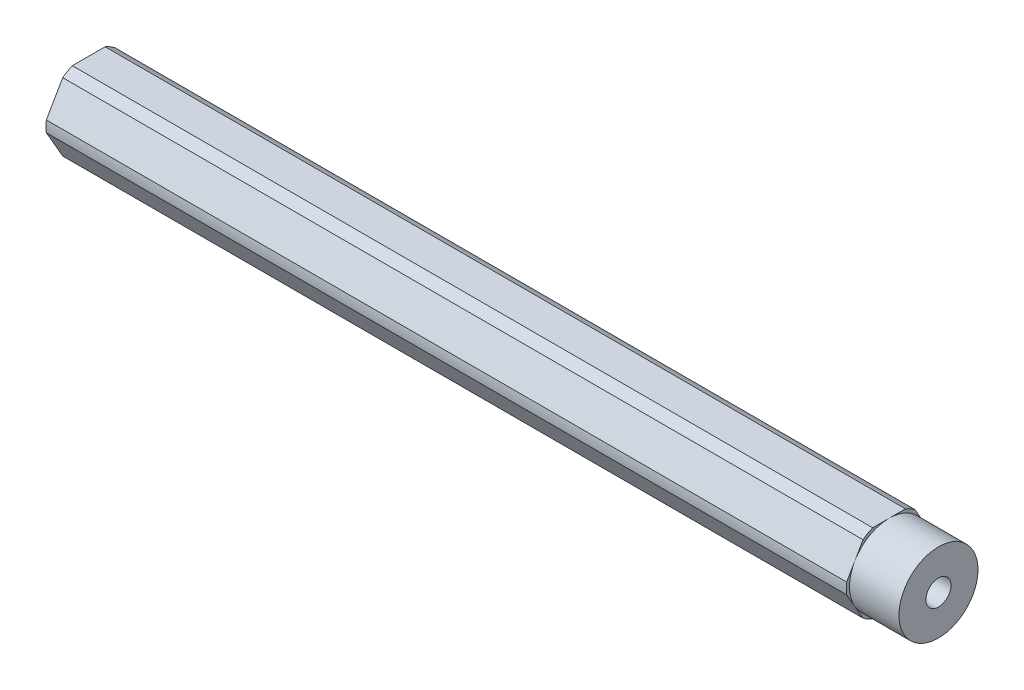
SolidWorks part; units mm, degrees
material "7075-T6 (SN)"
ref_plane "Front Plane" through (0, 0, 0) normal (0, 0, 1) x (1, 0, 0)
ref_plane "Top Plane" through (0, 0, 0) normal (0, 1, 0) x (1, 0, 0)
ref_plane "Right Plane" through (0, 0, 0) normal (1, 0, 0) x (0, 0, -1)
sketch "Sketch1" plane through (0, 0, 0) normal (1, 0, 0) x (0, 0, -1)
  line L1 (3.6662, 6.35) -> (-3.6662, 6.35)
  line L2 (-3.6662, 6.35) -> (-7.3323, 0)
  line L3 (-7.3323, 0) -> (-3.6662, -6.35)
  line L4 (-3.6662, -6.35) -> (3.6662, -6.35)
  line L5 (3.6662, -6.35) -> (7.3323, 0)
  line L6 (7.3323, 0) -> (3.6662, 6.35)
  circle A0 centre (0, 0) radius 6.875
  circle A1 centre (0, 0) radius 2.0193
  circle A2 centre (0, 0) radius 6.35 construction
  dimension "D1" = 12.7
  dimension "D2" = 13.75
  dimension "D3" = 4.0386
extrude "Boss-Extrude1" add sketch "Sketch1" along normal mid plane 136.525 contours L6 A0 L1 L2 L3 L4 L5 A1 region at (0, 5.7918, -3.3439)
hole_wizard "#10-32 Tapped Hole1" positions "3DSketch1" profile "Sketch2" tap size "#10-32" standard "ANSI Inch"
sketch3d "3DSketch1"
  circle A0 centre (-68.2625, 0, 0) radius 2.0193 construction
  circle A1 centre (68.2625, 0, 0) radius 2.0193 construction
  point P0 (68.2625, 0, 0)
  point P2 (-68.2625, 0, 0)
  point P7 (-66.2432, 0, 0)
  point P10 (70.2818, 0, 0)
sketch "Sketch2" plane through (68.2625, 0, 0) normal (0, 1, 0) x (0, 0, -1)
  line L0 (0, 0) -> (0, 17.5608)
  line L1 (0, 17.5608) -> (2.0193, 16.3474)
  line L2 (2.0193, 16.3474) -> (2.0193, 0)
  line L5 (2.0193, 0) -> (0, 0)
  line L10 (0, 17.5608) -> (-2.0193, 16.3474) construction
  line L11 (0, -6.35) -> (0, 107.95) construction
  dimension "Tap Drill Dia." = 4.0386
  dimension "Tap Drill Depth" = 16.3474
  dimension "Drill Angle" = 118
cosmetic thread "Hole Thread1" parameters "D1"=13.97, "D2"=4.826
cosmetic thread "Hole Thread2" parameters "D1"=13.97, "D2"=4.826
sketch "Sketch3" plane through (68.2625, 0, 0) normal (1, 0, 0) x (0, 0, -1)
  circle A0 centre (0, 0) radius 6.35
  dimension "D1" = 12.7
extrude "Cut-Extrude-Thin1" cut sketch "Sketch3" against normal blind 7.9375 thin thin type one direction wall 2.54
equation "\"D2@Sketch1\"=13.75mm"
